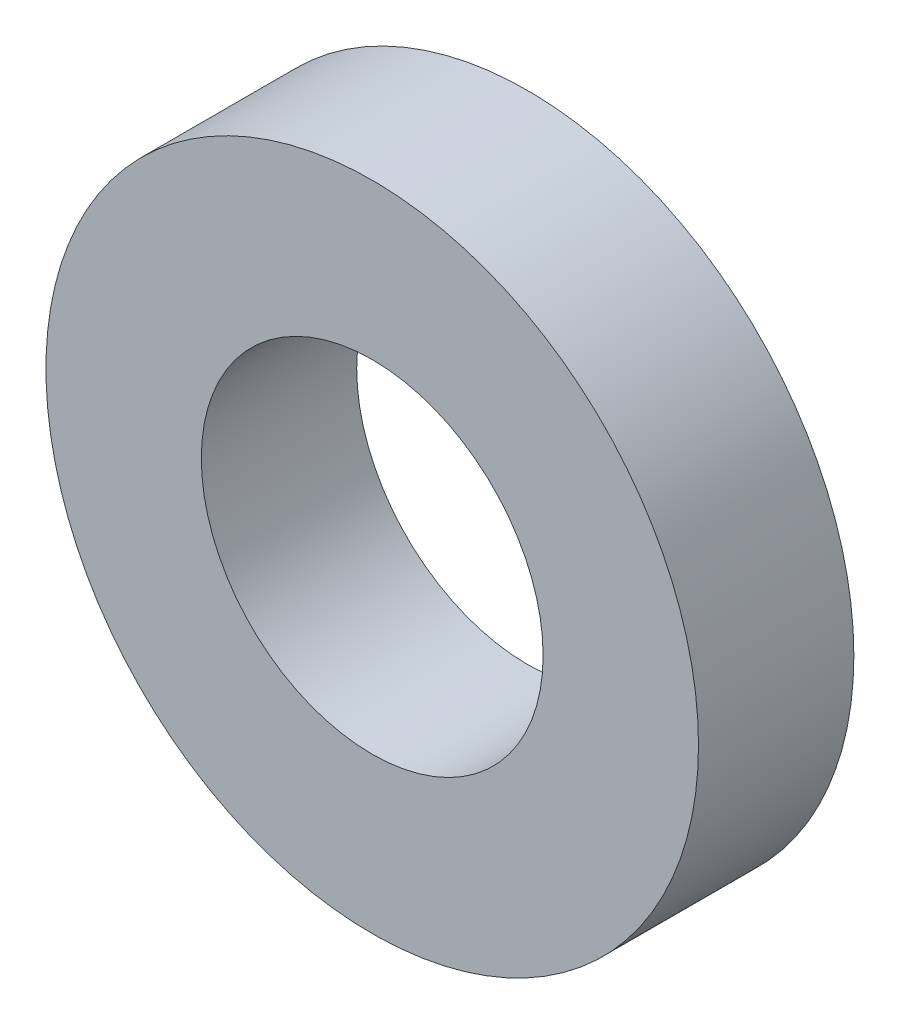
SolidWorks part; units mm, degrees
ref_plane "Front" through (0, 0, 0) normal (0, 0, 1) x (1, 0, 0)
ref_plane "Top" through (0, 0, 0) normal (0, 1, 0) x (1, 0, 0)
ref_plane "Right" through (0, 0, 0) normal (1, 0, 0) x (0, 0, -1)
sketch "Sketch1" plane through (0, 0, 0) normal (0, 0, 1) x (1, 0, 0)
  circle A0 centre (0, 0) radius 1.1
  circle A1 centre (0, 0) radius 2.1
  dimension "d" = 2.2
  dimension "D0" = 4.2
extrude "Base-Extrude" add sketch "Sketch1" against normal blind 1
